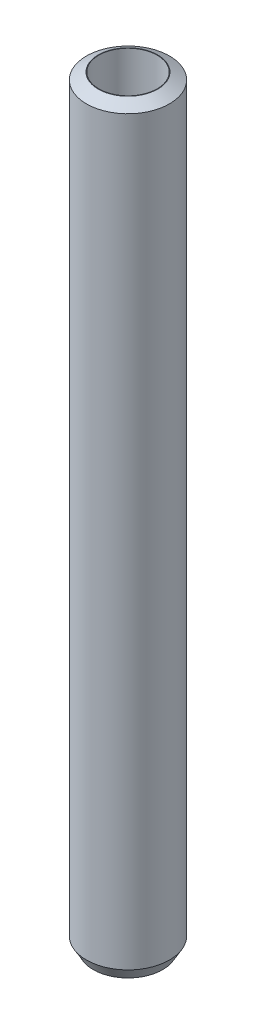
SolidWorks part; units mm, degrees
ref_plane "Front Plane" through (0, 0, 0) normal (0, 0, 1) x (1, 0, 0)
ref_plane "Top Plane" through (0, 0, 0) normal (0, 1, 0) x (1, 0, 0)
ref_plane "Right Plane" through (0, 0, 0) normal (1, 0, 0) x (0, 0, -1)
sketch "Sketch1" plane through (0, 0, 0) normal (0, 1, 0) x (1, 0, 0)
  circle A0 centre (0, 0) radius 25
  dimension "SHAFT_OD" = 50
extrude "Boss-Extrude1" add sketch "Sketch1" along normal blind 457.7074
sketch "Sketch2" plane through (0, 0, 0) normal (0, 1, 0) x (1, 0, 0)
  circle A0 centre (0, 0) radius 17.5719
  dimension "BORE_D" = 35.1439
extrude "Cut-Extrude1" cut sketch "Sketch2" along normal through all
chamfer "Chamfer1" distance 4.1099 angle 60 2 edges at (0, 457.7074, 25) (0, 0, 25) first distance on face at (0, 457.7074, 25) first distance on face at (0, 0, 17.5719)
